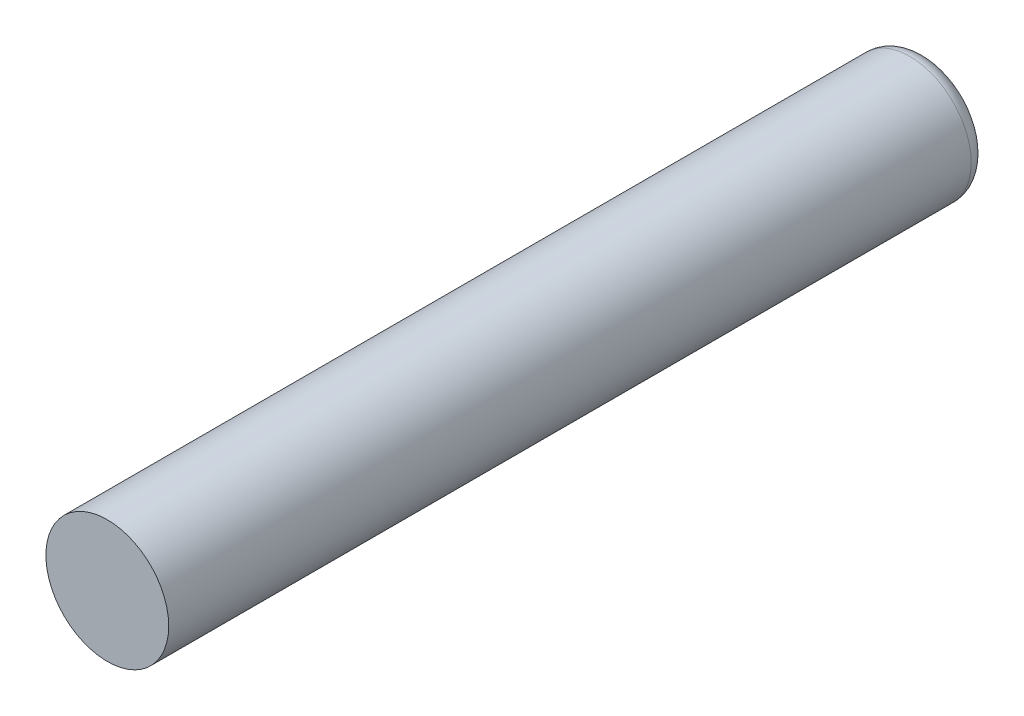
SolidWorks part; units mm, degrees
material "PUR"
ref_plane "Płaszczyzna przednia" through (0, 0, 0) normal (0, 0, 1) x (1, 0, 0)
ref_plane "Płaszczyzna górna" through (0, 0, 0) normal (0, 1, 0) x (1, 0, 0)
ref_plane "Płaszczyzna prawa" through (0, 0, 0) normal (1, 0, 0) x (0, 0, -1)
sketch "Szkic1" plane through (0, 0, 0) normal (0, 0, 1) x (1, 0, 0)
  circle A0 centre (0, 0) radius 15
extrude "Dodanie-wyciągnięcie1" add sketch "Szkic1" along normal blind 200
fillet "Zaokrąglenie1" radius 4 1 edges at (15, 0, 0)
